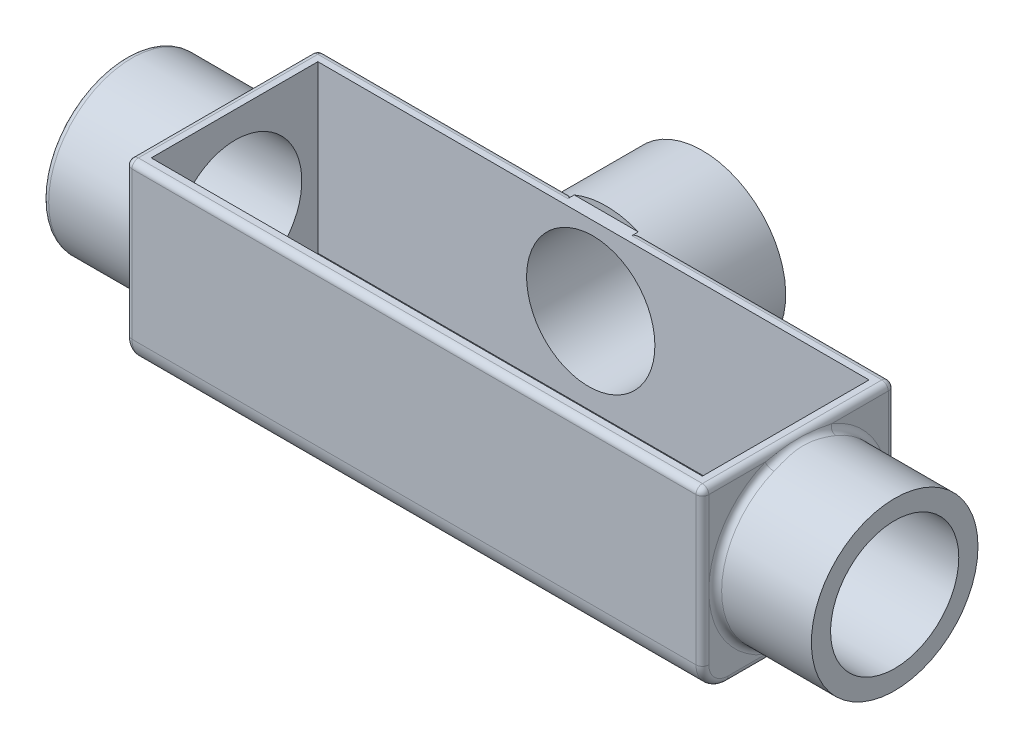
SolidWorks part; units mm, degrees
ref_plane "Alzado" through (0, 0, 0) normal (0, 0, 1) x (1, 0, 0)
ref_plane "Planta" through (0, 0, 0) normal (0, 1, 0) x (1, 0, 0)
ref_plane "Vista lateral" through (0, 0, 0) normal (1, 0, 0) x (0, 0, -1)
sketch "Croquis1" plane through (0, 0, 0) normal (0, 1, 0) x (1, 0, 0)
  line L0 (-50.6292, 0) -> (59.3708, 0) construction
  line L1 (-50.6292, 10) -> (-35.6292, 10)
  line L2 (-35.6292, 10) -> (-35.6292, 13)
  line L3 (-35.6292, 13) -> (-49.6292, 13)
  line L4 (-50.6292, 12) -> (-50.6292, 10)
  arc A0 (-50.6292, 12) -> (-49.6292, 13) centre (-49.6292, 12) cw
  point P9 (-50.6292, 13)
  dimension "D5" = 1
  dimension "D1" = 110
  dimension "D2" = 10
  dimension "D3" = 15
  dimension "D4" = 3
revolve "Revolución1" add sketch "Croquis1" angle 360 about L0
sketch "Croquis2" plane through (-35.6292, 0, 0) normal (1, 0, 0) x (0, 0, -1)
  line L1 (-11, -14) -> (11, -14)
  line L2 (-15, -10) -> (-15, 14)
  line L3 (-15, 14) -> (15, 14)
  line L4 (15, -10) -> (15, 14)
  line L5 (-15, -14) -> (15, 14) construction
  line L6 (-15, 14) -> (15, -14) construction
  arc A0 (15, -10) -> (11, -14) centre (11, -10) cw
  arc A1 (-11, -14) -> (-15, -10) centre (-11, -10) cw
  point P0 (0, 0)
  dimension "D2" = 4
  dimension "D1" = 30
extrude "Saliente-Extruir1" add sketch "Croquis2" along normal blind 90
sketch "Croquis3" plane through (0, 14, 0) normal (0, 1, 0) x (1, 0, 0)
  line L0 (9.3708, -15) -> (9.3708, 15) construction
  line L1 (54.3708, -15) -> (-35.6292, -15) construction
  line L2 (54.3708, 15) -> (-35.6292, 15) construction
  line L3 (54.3708, 15) -> (54.3708, -15) construction
  line L4 (-33.6292, -13) -> (52.3708, -13)
  line L5 (-33.6292, -13) -> (-33.6292, 13)
  line L6 (-33.6292, 13) -> (52.3708, 13)
  line L7 (52.3708, -13) -> (52.3708, 13)
  line L8 (-33.6292, -13) -> (52.3708, 13) construction
  line L9 (-33.6292, 13) -> (52.3708, -13) construction
  point P6 (9.3708, 0)
  dimension "D1" = 2
  dimension "D2" = 2
extrude "Cortar-Extruir1" cut sketch "Croquis3" against normal blind 25 draft 2
sketch "Croquis4" plane through (-35.6292, 0, 0) normal (-1, 0, 0) x (0, 0, 1)
  circle A0 centre (0, 0) radius 10
extrude "Cortar-Extruir2" cut sketch "Croquis4" against normal through all
sketch "Croquis5" plane through (54.3708, 0, 0) normal (1, 0, 0) x (0, 0, -1)
  circle A0 centre (0, 0) radius 10
  circle A1 centre (0, 0) radius 13
  dimension "D1" = 3
extrude "Saliente-Extruir2" add sketch "Croquis5" along normal blind 15
sketch "Croquis6" plane through (0, 0, -15) normal (0, 0, -1) x (-1, 0, 0)
  circle A0 centre (-9.3708, 2) radius 10
  dimension "D1" = 20
extrude "Cortar-Extruir3" cut sketch "Croquis6" against normal blind 15
sketch "Croquis7" plane through (0, 0, -15) normal (0, 0, -1) x (-1, 0, 0)
  circle A0 centre (-9.3708, 2) radius 10
  circle A1 centre (-9.3708, 2) radius 13
  dimension "D1" = 3
extrude "Saliente-Extruir3" add sketch "Croquis7" along normal blind 15
fillet "Redondeo2" radius 1 2 edges at (54.3708, 14, 0) (34.3708, 14, -15)
fillet "Redondeo3" radius 1 8 edges at (8.8708, 14, 15) (54.0779, 13.7071, 15) (54.3708, 1.5, 15) (54.3708, -12.8284, 13.8284) (54.3708, -14, 0) (54.3708, -12.8284, -13.8284) (54.0779, 13.7071, -14.7071) (54.3708, 1.5, -15)
fillet "Redondeo4" radius 1 2 edges at (54.3708, 0, 13) (54.3708, 0, -13)
fillet "Redondeo6" radius 1 8 edges at (-35.6292, 13.7071, 14.7071) (-35.6292, 1.5, 15) (-35.6292, -12.8284, 13.8284) (-35.6292, -14, 0) (-35.6292, -12.8284, -13.8284) (-15.6292, 14, -15) (-35.6292, 14, -0.5) (-35.6292, 2, -15)
